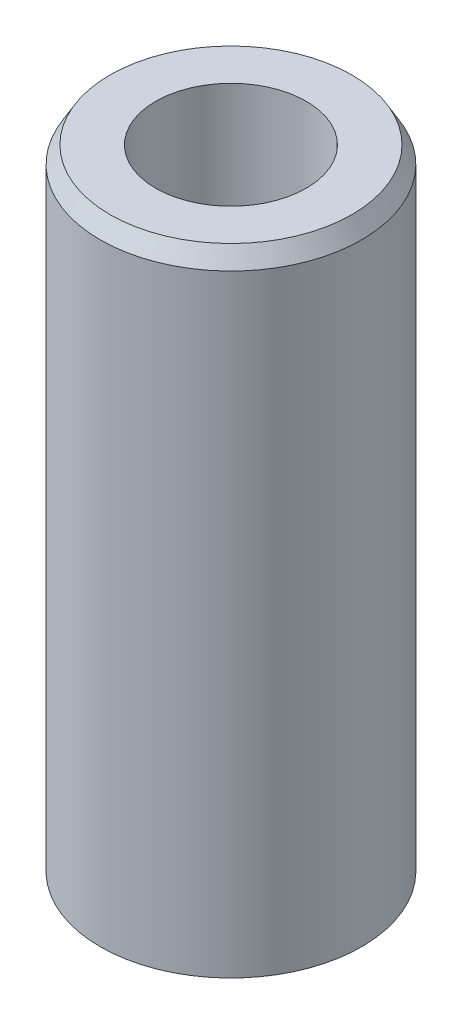
SolidWorks part; units mm, degrees
ref_plane "Front Plane" through (0, 0, 0) normal (0, 0, 1) x (1, 0, 0)
ref_plane "Top Plane" through (0, 0, 0) normal (0, 1, 0) x (1, 0, 0)
ref_plane "Right Plane" through (0, 0, 0) normal (1, 0, 0) x (0, 0, -1)
sketch "Sketch1" plane through (0, 0, 0) normal (0, 1, 0) x (1, 0, 0)
  circle A0 centre (0, 0) radius 40
  dimension "SHAFT_OD" = 80
extrude "Boss-Extrude1" add sketch "Sketch1" along normal blind 195.481
sketch "Sketch2" plane through (0, 0, 0) normal (0, 1, 0) x (1, 0, 0)
  circle A0 centre (0, 0) radius 23.0458
  dimension "BORE_D" = 46.0917
extrude "Cut-Extrude1" cut sketch "Sketch2" along normal through all
chamfer "Chamfer1" distance 5.1843 angle 30 2 edges at (0, 195.481, 40) (0, 0, 40) first distance on face at (0, 195.481, 40) first distance on face at (0, 0, 23.0458)
